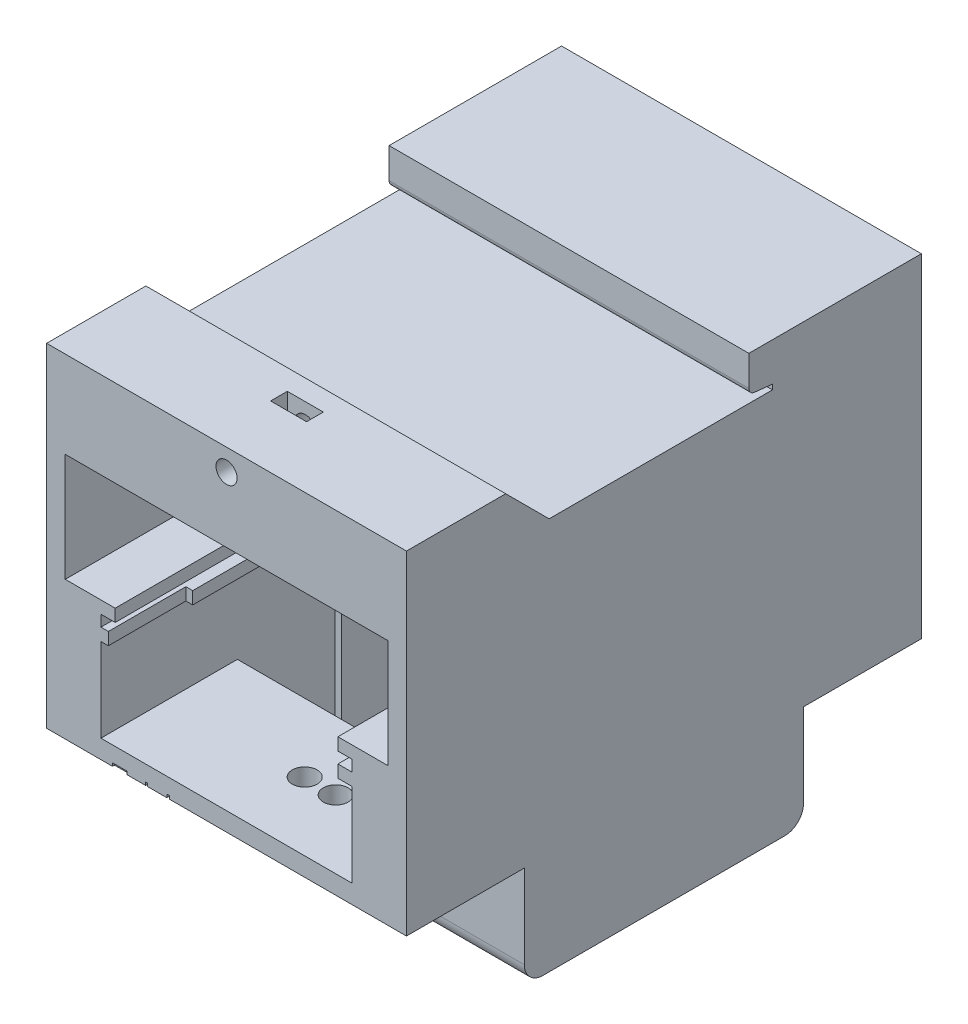
SolidWorks part; units mm, degrees
ref_plane "Plan de face" through (0, 0, 0) normal (0, 0, 1) x (1, 0, 0)
ref_plane "Plan de dessus" through (0, 0, 0) normal (0, 1, 0) x (1, 0, 0)
ref_plane "Plan de droite" through (0, 0, 0) normal (1, 0, 0) x (0, 0, -1)
sketch "Esquisse1" plane through (0, 0, 0) normal (0, 0, 1) x (1, 0, 0)
  line L0 (-20.25, 0) -> (-17.95, 0)
  line L1 (-17.95, 0) -> (-17.95, -2)
  line L2 (-17.95, -2) -> (-20.25, -2)
  line L3 (-20.25, -2) -> (-20.25, -15.5)
  line L14 (0, 21.25) -> (-26, 21.25)
  line L15 (-26, 21.25) -> (-26, 3.8)
  line L16 (-26, 3.8) -> (-17.95, 3.8)
  line L17 (-17.95, 3.8) -> (-17.95, 1.8)
  line L18 (-17.95, 1.8) -> (-20.25, 1.8)
  line L19 (-20.25, 1.8) -> (-20.25, 0)
  line L20 (0, 0) -> (0, 31.1961) construction
  line L21 (0, 0) -> (0, -22.5264) construction
  line L22 (-20.25, -15.5) -> (20.25, -15.5)
  line L23 (29, 28.25) -> (-29, 28.25)
  line L24 (-29, 28.25) -> (-29, -18.5)
  line L25 (-29, -18.5) -> (29, -18.5)
  line L26 (29, 28.25) -> (29, -18.5)
  line L27 (20.25, 1.8) -> (20.25, 0)
  line L28 (17.95, 1.8) -> (20.25, 1.8)
  line L29 (17.95, 3.8) -> (17.95, 1.8)
  line L30 (26, 3.8) -> (17.95, 3.8)
  line L31 (26, 21.25) -> (26, 3.8)
  line L32 (0, 21.25) -> (26, 21.25)
  line L33 (20.25, -2) -> (20.25, -15.5)
  line L34 (17.95, -2) -> (20.25, -2)
  line L35 (17.95, 0) -> (17.95, -2)
  line L36 (20.25, 0) -> (17.95, 0)
  point P15 (0, -18.5)
  point P16 (0, 28.25)
  point P22 (0, -15.5)
  dimension "D1" = 40.5
  dimension "D2" = 15.5
  dimension "D3" = 2.3
  dimension "D5" = 3
  dimension "D6" = 7
  dimension "D7" = 3
  dimension "D8" = 2
  dimension "D9" = 1.8
  dimension "D10" = 2
  dimension "D11" = 21.25
  dimension "D12" = 52
extrude "Boss.-Extru.1" add sketch "Esquisse1" along normal blind 65
sketch "Esquisse2" plane through (0, 0, 0) normal (0, 0, 1) x (1, 0, 0)
  line L6 (26, 3.8) -> (-26, 3.8)
  line L7 (-20.25, -2) -> (20.25, -2) construction
  line L14 (-29, 28.25) -> (-29, -18.5)
  line L15 (29, 28.25) -> (-29, 28.25)
  line L16 (29, -18.5) -> (29, 28.25)
  line L17 (-29, -18.5) -> (29, -18.5)
  line L18 (-29, 28.25) -> (-29, -18.5)
  line L19 (29, 28.25) -> (-29, 28.25)
  line L20 (29, -18.5) -> (29, 28.25)
  line L21 (-29, -18.5) -> (29, -18.5)
  line L38 (-17.95, 0) -> (-17.95, -2)
  line L39 (-17.95, -2) -> (-20.25, -2)
  line L40 (-20.25, -2) -> (-20.25, -15.5)
  line L41 (-20.25, -15.5) -> (20.25, -15.5)
  line L42 (20.25, -15.5) -> (20.25, -2)
  line L43 (20.25, -2) -> (17.95, -2)
  line L44 (17.95, -2) -> (17.95, 0)
  line L45 (17.95, 0) -> (20.25, 0)
  line L46 (20.25, 0) -> (20.25, 1.8)
  line L47 (20.25, 1.8) -> (17.95, 1.8)
  line L63 (17.95, 1.8) -> (17.95, 3.8)
  line L64 (17.95, 3.8) -> (26, 3.8)
  line L65 (26, 3.8) -> (26, 21.25)
  line L66 (26, 21.25) -> (-26, 21.25)
  line L67 (-26, 21.25) -> (-26, 3.8)
  line L68 (-26, 3.8) -> (-17.95, 3.8)
  line L69 (-17.95, 3.8) -> (-17.95, 1.8)
  line L70 (-17.95, 1.8) -> (-20.25, 1.8)
  line L71 (-20.25, 1.8) -> (-20.25, 0)
  line L72 (-20.25, 0) -> (-17.95, 0)
  line L75 (-20.25, -2) -> (-20.25, -15.5) construction
  line L76 (-20.25, -15.5) -> (20.25, -15.5) construction
  line L77 (20.25, -15.5) -> (20.25, -2) construction
  line L85 (26, 3.8) -> (26, 21.25)
  line L86 (26, 21.25) -> (-26, 21.25)
  line L87 (-26, 21.25) -> (-26, 3.8)
  dimension "D1" = 0
  dimension "D2" = 0
extrude "Boss.-Extru.2" add sketch "Esquisse2" against normal blind 15
sketch "Esquisse3" plane through (0, 0, -15) normal (0, 0, -1) x (-1, 0, 0)
  line L4 (-29, -18.5) -> (29, -18.5)
  line L5 (29, -18.5) -> (29, 28.25)
  line L6 (29, 28.25) -> (-29, 28.25)
  line L7 (-29, 28.25) -> (-29, -18.5)
  line L8 (-29, -18.5) -> (29, -18.5)
  line L9 (29, -18.5) -> (29, 28.25)
  line L10 (29, 28.25) -> (-29, 28.25)
  line L11 (-29, 28.25) -> (-29, -18.5)
  dimension "D1" = 0
extrude "Boss.-Extru.3" add sketch "Esquisse3" along normal blind 3
sketch "Esquisse4" plane through (0, 0, 65) normal (0, 0, 1) x (1, 0, 0)
  line L0 (-20.25, 0) -> (-17.95, 0) construction
  line L1 (-8.75, -15.1) -> (-19.05, -15.1)
  line L2 (-8.75, -15.1) -> (-8.75, 0)
  line L3 (-8.75, 0) -> (-19.05, 0)
  line L4 (-19.05, -15.1) -> (-19.05, 0)
  line L5 (-8.75, 0) -> (-8.75, -9.1) construction
  line L6 (-8.75, -15.1) -> (-18.75, -15.1) construction
  line L7 (-18.75, -9.1) -> (-18.75, -13.9) construction
  dimension "D1" = 0.3
extrude "Enlèv. mat.-Extru.1" cut sketch "Esquisse4" against normal up to vertex (12.5 mm away)
sketch "Esquisse5" plane through (0, -18.5, 0) normal (0, -1, 0) x (1, 0, 0)
  circle A0 centre (1.5962, 54) radius 1.5 construction
  circle A1 centre (1.5962, 54) radius 1.5 construction
  circle A2 centre (6.5962, 54) radius 1.5 construction
  circle A3 centre (6.5962, 54) radius 1.5 construction
  circle A4 centre (1.5962, 54) radius 2
  circle A5 centre (6.5962, 54) radius 2
  arc A6 (-11.25, 70.5677) -> (-11.25, 67.0677) centre (-11.25, 68.8177) ccw construction
  arc A7 (-11.25, 70.5677) -> (-11.25, 67.0677) centre (-11.25, 68.8177) ccw construction
  arc A8 (-11.25, 67.0677) -> (-11.25, 70.5677) centre (-11.25, 68.8177) ccw construction
  arc A9 (-11.25, 67.0677) -> (-11.25, 70.5677) centre (-11.25, 68.8177) ccw construction
  arc A10 (-16.25, 70.5677) -> (-16.25, 67.0677) centre (-16.25, 68.8177) ccw construction
  arc A11 (-16.25, 70.5677) -> (-16.25, 67.0677) centre (-16.25, 68.8177) ccw construction
  arc A12 (-16.25, 67.0677) -> (-16.25, 70.5677) centre (-16.25, 68.8177) ccw construction
  arc A13 (-16.25, 67.0677) -> (-16.25, 70.5677) centre (-16.25, 68.8177) ccw construction
  arc A14 (-11.25, 71.0677) -> (-11.25, 66.5677) centre (-11.25, 68.8177) ccw construction
  arc A15 (-11.25, 66.5677) -> (-11.25, 71.0677) centre (-11.25, 68.8177) ccw construction
  arc A16 (-16.25, 71.0677) -> (-16.25, 66.5677) centre (-16.25, 68.8177) ccw construction
  arc A17 (-16.25, 66.5677) -> (-16.25, 71.0677) centre (-16.25, 68.8177) ccw construction
  dimension "D1" = 0.5
  dimension "D2" = 0.5
extrude "Enlèv. mat.-Extru.2" cut sketch "Esquisse5" against normal up to next
sketch "Esquisse6" plane through (0, -18.5, 0) normal (0, -1, 0) x (1, 0, 0)
  line L0 (10.4775, 60.689) -> (-2.1281, 60.689) construction
  line L1 (-7.6073, 65.1874) -> (-19.5069, 65.1874) construction
  text T0 "T1 T2"
  text T1 "NL" font "Century Gothic" height 5
extrude "Enlèv. mat.-Extru.3" cut sketch "Esquisse6" against normal blind 0.5
sketch "Esquisse7" plane through (0, -18.5, 0) normal (0, -1, 0) x (1, 0, 0)
  line L0 (-29, 65) -> (-29, -18) construction
  line L1 (-29, 1) -> (29, 1)
  line L2 (-29, 1) -> (-29, 46)
  line L3 (-29, 46) -> (29, 46)
  line L4 (29, 1) -> (29, 46)
  line L5 (29, 65) -> (29, -18) construction
  line L6 (29, -18) -> (-29, -18) construction
  line L7 (-29, 65) -> (-18.3776, 65) construction
  dimension "D1" = 19
  dimension "D2" = 19
extrude "Boss.-Extru.4" add sketch "Esquisse7" along normal blind 16.5
sketch "Esquisse8" plane through (0, -15.5, 0) normal (0, 1, 0) x (1, 0, 0)
  line L0 (-20.25, -65) -> (-20.25, 0) construction
  line L1 (-20.25, -43) -> (20.25, -43)
  line L2 (-20.25, -43) -> (-20.25, -4)
  line L3 (-20.25, -4) -> (20.25, -4)
  line L4 (20.25, -43) -> (20.25, -4)
  line L5 (20.25, -65) -> (20.25, 0) construction
  line L6 (-29, -1) -> (29, -1) construction
  line L7 (29, -46) -> (-29, -46) construction
  dimension "D1" = 3
  dimension "D2" = 3
extrude "Enlèv. mat.-Extru.4" cut sketch "Esquisse8" against normal offset from surface (16.5 mm away) 3 up to face at (0, -35, 23.5)
fillet "Congé2" radius 3 2 edges at (0, -35, 1) (0, -35, 46)
sketch "Esquisse9" plane through (-29, 0, 0) normal (-1, 0, 0) x (0, 0, 1)
  line L1 (-18, 28.25) -> (6, 28.25)
  line L2 (-18, 28.25) -> (-18, 35.25)
  line L3 (-18, 35.25) -> (9.8, 35.25)
  line L4 (9.8, 29.45) -> (9.8, 35.25)
  line L7 (9.8, 29.45) -> (6, 29.05)
  line L8 (6, 29.05) -> (6, 28.25)
  line L10 (65, 28.25) -> (42, 28.25)
  line L11 (65, 28.25) -> (65, 35.25)
  line L12 (65, 35.25) -> (49, 35.25)
  line L13 (42, 28.25) -> (49, 35.25)
  point P12 (32, 32.25)
  point P13 (33.4653, 32.25)
  dimension "D1" = 0.8
  dimension "D2" = 1.2
  dimension "D3" = 3.8
  dimension "D4" = 24
  dimension "D5" = 7
  dimension "D6" = 36
  dimension "D7" = 45
extrude "Boss.-Extru.5" add sketch "Esquisse9" against normal up to surface (58 mm away) up to face at (29, -15.2743, 23.5)
sketch "Esquisse10" plane through (0, -35, 0) normal (0, -1, 0) x (1, 0, 0)
  line L0 (29, 15) -> (-29, 15) construction
  line L1 (29, 4) -> (29, 43) construction
  line L2 (-29, 43) -> (-29, 4) construction
  line L3 (-29, 4) -> (29, 4) construction
  text T0 "TIC -> MQTT" font "Stencil" height 6.5
  dimension "D1" = 11
extrude "Enlèv. mat.-Extru.5" cut sketch "Esquisse10" against normal blind 0.5
hole_wizard "Dégagement M31" positions "Esquisse11" profile "Esquisse13" hole size "M3" standard "Ansi Metric"
sketch "Esquisse11" plane through (0, 0, 65) normal (0, 0, 1) x (1, 0, 0)
  line L0 (-29, 35.25) -> (29, 28.25) construction
  point P0 (0, 31.75)
  point P9 (0, 31.75)
sketch "Esquisse13" plane through (0, 31.75, 65) normal (1, 0, 0) x (0, -1, 0)
  line L0 (0, 0) -> (0, 19.5)
  line L1 (0, 19.5) -> (1.7, 19.5)
  line L2 (1.7, 19.5) -> (1.7, 0)
  line L5 (1.7, 0) -> (0, 0)
  line L11 (0, -6.35) -> (0, 107.95) construction
  dimension "Diamètre du perçage jusqu'au prochain" = 3.4
  dimension "Profondeur du perçage jusqu'au prochain" = 19.5
sketch "Esquisse14" plane through (0, 0, 65) normal (0, 0, 1) x (1, 0, 0)
  line L0 (-2.9, 33.4243) -> (-2.9, 35.25)
  line L1 (0, 28.4014) -> (2.9, 30.0757)
  line L2 (2.9, 30.0757) -> (2.9, 33.4243)
  line L3 (2.9, 33.4243) -> (0, 35.0986) construction
  line L4 (0, 35.0986) -> (-2.9, 33.4243) construction
  line L5 (-2.9, 33.4243) -> (-2.9, 30.0757)
  line L6 (-2.9, 30.0757) -> (0, 28.4014)
  line L7 (29, 35.25) -> (-29, 35.25) construction
  line L8 (-2.9, 35.25) -> (2.9, 35.25)
  line L9 (2.9, 35.25) -> (2.9, 33.4243)
  circle A0 centre (0, 31.75) radius 2.9 construction
  dimension "D1" = 5.8
extrude "Enlèv. mat.-Extru.6" cut sketch "Esquisse14" against normal blind 2.7 from offset 10 offset against normal yes
hole_wizard "Diamètre du perçage Ø1.5 (1.5)1" positions "Esquisse16" profile "Esquisse17" hole size "Ø1.5" standard "Ansi Metric"
sketch "Esquisse16" plane through (0, -35, 0) normal (0, -1, 0) x (-1, 0, 0)
  line L0 (17.95, -52.5) -> (17.95, 0) construction
  line L1 (-17.95, -65) -> (-17.95, 0) construction
  line L2 (13.95, -19.2295) -> (-13.95, -19.2295) construction
  point P0 (13.95, -19.2295)
  point P2 (-13.95, -19.2295)
  dimension "D1" = 4
  dimension "D2" = 4
sketch "Esquisse17" plane through (-13.95, -35, 19.2295) normal (1, 0, 0) x (0, 0, -1)
  line L0 (0, 0) -> (0, 3)
  line L1 (0, 3) -> (0.75, 3)
  line L2 (0.75, 3) -> (0.75, 0)
  line L5 (0.75, 0) -> (0, 0)
  line L11 (0, -6.35) -> (0, 107.95) construction
  dimension "Diamètre du perçage jusqu'au prochain" = 1.5
  dimension "Profondeur du perçage jusqu'au prochain" = 3
sketch "Esquisse18" plane through (0, -32, 0) normal (0, 1, 0) x (1, 0, 0)
  line L0 (-20.25, -4) -> (20.25, -4) construction
  line L1 (-4.5, -4) -> (-3.5, -4)
  line L2 (-4.5, -4) -> (-4.5, -43)
  line L3 (-4.5, -43) -> (-3.5, -43)
  line L4 (-3.5, -4) -> (-3.5, -43)
  line L5 (-20.25, -43) -> (20.25, -43) construction
  line L6 (-4, -4) -> (-4, -43) construction
  dimension "D1" = 1
  dimension "D2" = 4
extrude "Boss.-Extru.6" add sketch "Esquisse18" along normal up to surface (32 mm away) up to face at (19.1, 0, 32.5)
sketch "Esquisse20" plane through (0, -35, 0) normal (0, -1, 0) x (1, 0, 0)
  line L0 (-13.7598, 34.7762) -> (-11.2979, 32.3143)
  line L1 (-11.2979, 32.3143) -> (-11.8871, 31.7462)
  line L2 (-11.8871, 31.7462) -> (-12.0554, 31.7882)
  line L3 (-12.0554, 31.7882) -> (-12.5262, 31.5857)
  line L4 (-12.5262, 31.5857) -> (-12.7288, 31.1149)
  line L5 (-12.7288, 31.1149) -> (-12.5262, 30.6362)
  line L6 (-12.5262, 30.6362) -> (-12.0554, 30.4416)
  line L7 (-12.0554, 30.4416) -> (-11.5767, 30.6362)
  line L8 (-11.5767, 30.6362) -> (-11.3821, 31.1149)
  line L9 (-11.3821, 31.1149) -> (-11.4031, 31.2622)
  line L10 (-11.4031, 31.2622) -> (-10.835, 31.8514)
  line L11 (-10.835, 31.8514) -> (-8.3731, 29.3895)
  line L12 (-8.3731, 29.3895) -> (-8.0943, 29.2948)
  line L13 (-8.0943, 29.2948) -> (-7.8471, 29.4526)
  line L14 (-7.8471, 29.4526) -> (-7.3973, 30.7483)
  line L15 (-7.3973, 30.7483) -> (-7.3737, 32.1012)
  line L16 (-7.3737, 32.1012) -> (-7.7761, 33.4029)
  line L17 (-7.7761, 33.4029) -> (-8.6046, 34.5447)
  line L18 (-8.6046, 34.5447) -> (-9.7464, 35.3732)
  line L19 (-9.7464, 35.3732) -> (-11.0481, 35.7756)
  line L20 (-11.0481, 35.7756) -> (-12.401, 35.752)
  line L21 (-12.401, 35.752) -> (-13.6967, 35.3022)
  line L22 (-13.6967, 35.3022) -> (-13.8545, 35.055)
  line L23 (-13.8545, 35.055) -> (-13.7598, 34.7762)
  line L24 (-18.0943, 31.4305) -> (-17.9137, 30.1727)
  line L25 (-17.9137, 30.1727) -> (-17.5128, 29.0022)
  line L26 (-17.5128, 29.0022) -> (-16.9141, 27.9411)
  line L27 (-16.9141, 27.9411) -> (-16.1401, 27.0118)
  line L28 (-16.1401, 27.0118) -> (-15.2133, 26.2363)
  line L29 (-15.2133, 26.2363) -> (-14.156, 25.6368)
  line L30 (-14.156, 25.6368) -> (-12.9907, 25.2357)
  line L31 (-12.9907, 25.2357) -> (-11.7398, 25.0549)
  line L32 (-11.7398, 25.0549) -> (-11.7187, 25.0339)
  line L33 (-11.7187, 25.0339) -> (-11.4794, 25.1417)
  line L34 (-11.4794, 25.1417) -> (-11.3821, 25.3916)
  line L35 (-11.3821, 25.3916) -> (-11.3821, 26.0439)
  line L36 (-11.3821, 26.0439) -> (-11.4689, 26.2832)
  line L37 (-11.4689, 26.2832) -> (-11.6977, 26.3805)
  line L38 (-11.6977, 26.3805) -> (-12.688, 26.5294)
  line L39 (-12.688, 26.5294) -> (-13.6112, 26.8536)
  line L40 (-13.6112, 26.8536) -> (-14.4496, 27.3352)
  line L41 (-14.4496, 27.3352) -> (-15.1854, 27.956)
  line L42 (-15.1854, 27.956) -> (-15.8008, 28.6982)
  line L43 (-15.8008, 28.6982) -> (-16.2782, 29.5437)
  line L44 (-16.2782, 29.5437) -> (-16.5998, 30.4745)
  line L45 (-16.5998, 30.4745) -> (-16.7477, 31.4726)
  line L46 (-16.7477, 31.4726) -> (-16.8608, 31.6936)
  line L47 (-16.8608, 31.6936) -> (-17.0844, 31.7882)
  line L48 (-17.0844, 31.7882) -> (-17.7577, 31.7882)
  line L49 (-17.7577, 31.7882) -> (-18.0076, 31.6804)
  line L50 (-18.0076, 31.6804) -> (-18.1154, 31.4305)
  line L51 (-18.1154, 31.4305) -> (-18.0943, 31.4305)
  line L52 (-16.0743, 31.4095) -> (-15.9347, 30.5656)
  line L53 (-15.9347, 30.5656) -> (-15.6516, 29.7794)
  line L54 (-15.6516, 29.7794) -> (-14.7119, 28.4373)
  line L55 (-14.7119, 28.4373) -> (-13.3699, 27.4977)
  line L56 (-13.3699, 27.4977) -> (-12.5837, 27.2145)
  line L57 (-12.5837, 27.2145) -> (-11.7398, 27.0749)
  line L58 (-11.7398, 27.0749) -> (-11.7187, 27.0538)
  line L59 (-11.7187, 27.0538) -> (-11.4794, 27.1617)
  line L60 (-11.4794, 27.1617) -> (-11.3821, 27.4116)
  line L61 (-11.3821, 27.4116) -> (-11.3821, 28.0849)
  line L62 (-11.3821, 28.0849) -> (-11.4663, 28.3085)
  line L63 (-11.4663, 28.3085) -> (-11.6767, 28.4216)
  line L64 (-11.6767, 28.4216) -> (-12.8162, 28.7237)
  line L65 (-12.8162, 28.7237) -> (-13.7545, 29.3868)
  line L66 (-13.7545, 29.3868) -> (-14.4167, 30.3301)
  line L67 (-14.4167, 30.3301) -> (-14.7277, 31.4726)
  line L68 (-14.7277, 31.4726) -> (-14.8408, 31.6935)
  line L69 (-14.8408, 31.6935) -> (-15.0644, 31.7882)
  line L70 (-15.0644, 31.7882) -> (-15.7377, 31.7882)
  line L71 (-15.7377, 31.7882) -> (-15.9876, 31.6804)
  line L72 (-15.9876, 31.6804) -> (-16.0954, 31.4305)
  line L73 (-16.0954, 31.4305) -> (-16.0743, 31.4095)
  line L74 (11.9784, 35.4617) -> (18.7117, 35.4616)
  line L75 (18.7117, 35.4616) -> (18.9511, 35.5669)
  line L76 (18.9511, 35.5669) -> (19.0484, 35.7983)
  line L77 (19.0484, 35.7983) -> (19.0483, 36.4716)
  line L78 (19.0483, 36.4716) -> (18.951, 36.711)
  line L79 (18.951, 36.711) -> (18.7116, 36.8083)
  line L80 (18.7116, 36.8083) -> (11.9783, 36.8083)
  line L81 (11.9783, 36.8083) -> (11.7469, 36.711)
  line L82 (11.7469, 36.711) -> (11.6416, 36.4716)
  line L83 (11.6416, 36.4716) -> (11.6417, 35.7983)
  line L84 (11.6417, 35.7983) -> (11.7469, 35.5669)
  line L85 (11.7469, 35.5669) -> (11.9784, 35.4617)
  line L86 (7.6017, 28.7283) -> (7.6017, 27.7183)
  line L87 (7.6017, 27.7183) -> (7.7069, 27.4869)
  line L88 (7.7069, 27.4869) -> (7.9384, 27.3817)
  line L89 (7.9384, 27.3817) -> (8.1777, 27.4869)
  line L90 (8.1777, 27.4869) -> (8.275, 27.7183)
  line L91 (8.275, 27.7183) -> (8.275, 28.7283)
  line L92 (8.275, 28.7283) -> (8.9483, 28.7283)
  line L93 (8.9483, 28.7283) -> (8.9483, 27.7183)
  line L94 (8.9483, 27.7183) -> (9.0535, 27.4869)
  line L95 (9.0535, 27.4869) -> (9.285, 27.3817)
  line L96 (9.285, 27.3817) -> (9.5243, 27.4869)
  line L97 (9.5243, 27.4869) -> (9.6216, 27.7183)
  line L98 (9.6216, 27.7183) -> (9.6217, 28.7283)
  line L99 (9.6217, 28.7283) -> (9.9583, 28.7283)
  line L100 (9.9583, 28.7283) -> (10.1977, 28.8335)
  line L101 (10.1977, 28.8335) -> (10.295, 29.065)
  line L102 (10.295, 29.065) -> (10.295, 29.7383)
  line L103 (10.295, 29.7383) -> (10.2085, 30.2782)
  line L104 (10.2085, 30.2782) -> (9.9662, 30.7431)
  line L105 (9.9662, 30.7431) -> (9.5937, 31.1054)
  line L106 (9.5937, 31.1054) -> (9.1167, 31.3375)
  line L107 (9.1167, 31.3375) -> (9.1167, 33.8414)
  line L108 (9.1167, 33.8414) -> (9.2587, 34.2412)
  line L109 (9.2587, 34.2412) -> (9.6217, 34.4516)
  line L110 (9.6217, 34.4516) -> (10.0925, 34.3149)
  line L111 (10.0925, 34.3149) -> (10.295, 33.8625)
  line L112 (10.295, 33.8625) -> (10.295, 33.2733)
  line L113 (10.295, 33.2733) -> (10.4423, 32.5579)
  line L114 (10.4423, 32.5579) -> (10.8421, 31.9687)
  line L115 (10.8421, 31.9687) -> (11.4313, 31.5689)
  line L116 (11.4313, 31.5689) -> (12.1467, 31.4217)
  line L117 (12.1467, 31.4217) -> (12.315, 31.4217)
  line L118 (12.315, 31.4217) -> (12.315, 27.3817)
  line L119 (12.315, 27.3817) -> (12.4219, 26.8605)
  line L120 (12.4219, 26.8605) -> (12.7122, 26.4322)
  line L121 (12.7122, 26.4322) -> (13.1406, 26.1418)
  line L122 (13.1406, 26.1418) -> (13.6617, 26.035)
  line L123 (13.6617, 26.035) -> (17.0283, 26.035)
  line L124 (17.0283, 26.035) -> (17.5583, 26.1418)
  line L125 (17.5583, 26.1418) -> (17.9857, 26.4322)
  line L126 (17.9857, 26.4322) -> (18.2711, 26.8606)
  line L127 (18.2711, 26.8606) -> (18.375, 27.3817)
  line L128 (18.375, 27.3817) -> (18.375, 34.7883)
  line L129 (18.375, 34.7883) -> (12.315, 34.7883)
  line L130 (12.315, 34.7883) -> (12.315, 32.4317)
  line L131 (12.315, 32.4317) -> (12.1467, 32.4317)
  line L132 (12.1467, 32.4317) -> (11.5523, 32.6789)
  line L133 (11.5523, 32.6789) -> (11.305, 33.2733)
  line L134 (11.305, 33.2733) -> (11.305, 33.7994)
  line L135 (11.305, 33.7994) -> (11.1998, 34.4023)
  line L136 (11.1998, 34.4023) -> (10.9052, 34.9146)
  line L137 (10.9052, 34.9146) -> (10.4528, 35.2848)
  line L138 (10.4528, 35.2848) -> (9.8742, 35.4616)
  line L139 (9.8742, 35.4616) -> (9.1985, 35.3893)
  line L140 (9.1985, 35.3893) -> (8.6354, 35.0566)
  line L141 (8.6354, 35.0566) -> (8.2497, 34.5266)
  line L142 (8.2497, 34.5266) -> (8.1067, 33.8625)
  line L143 (8.1067, 33.8625) -> (8.1067, 31.3375)
  line L144 (8.1067, 31.3375) -> (7.6385, 31.1054)
  line L145 (7.6385, 31.1054) -> (7.265, 30.7431)
  line L146 (7.265, 30.7431) -> (7.0178, 30.2782)
  line L147 (7.0178, 30.2782) -> (6.9284, 29.7383)
  line L148 (6.9284, 29.7383) -> (6.9284, 29.065)
  line L149 (6.9284, 29.065) -> (7.0336, 28.8335)
  line L150 (7.0336, 28.8335) -> (7.2651, 28.7283)
  line L151 (7.2651, 28.7283) -> (7.6017, 28.7283)
  line L152 (13.5776, 29.7383) -> (15.5554, 32.6631)
  line L153 (15.5554, 32.6631) -> (15.7658, 32.7683)
  line L154 (15.7658, 32.7683) -> (15.971, 32.6894)
  line L155 (15.971, 32.6894) -> (16.0183, 32.5158)
  line L156 (16.0183, 32.5158) -> (15.5343, 30.7483)
  line L157 (15.5343, 30.7483) -> (16.7758, 30.7483)
  line L158 (16.7758, 30.7483) -> (16.9731, 30.6799)
  line L159 (16.9731, 30.6799) -> (17.0283, 30.5169)
  line L160 (17.0283, 30.5169) -> (16.6916, 28.2654)
  line L161 (16.6916, 28.2654) -> (16.4391, 28.055)
  line L162 (16.4391, 28.055) -> (15.0083, 28.055)
  line L163 (15.0083, 28.055) -> (14.8216, 28.147)
  line L164 (14.8216, 28.147) -> (14.7769, 28.3496)
  line L165 (14.7769, 28.3496) -> (15.0083, 29.4017)
  line L166 (15.0083, 29.4017) -> (13.809, 29.4017)
  line L167 (13.809, 29.4017) -> (13.5907, 29.5148)
  line L168 (13.5907, 29.5148) -> (13.5776, 29.7383)
  line L169 (40.8425, 17.0939) -> (39.2012, 15.4527) construction
  line L170 (39.2012, 15.4527) -> (39.1065, 15.2212) construction
  line L171 (39.1065, 15.2212) -> (39.2012, 14.9897) construction
  line L172 (39.2012, 14.9897) -> (39.6852, 14.5058) construction
  line L173 (39.6852, 14.5058) -> (39.9166, 14.4111) construction
  line L174 (39.9166, 14.4111) -> (40.1481, 14.5058) construction
  line L175 (40.1481, 14.5058) -> (41.7893, 16.147) construction
  line L176 (41.7893, 16.147) -> (43.5568, 14.3795) construction
  line L177 (43.5568, 14.3795) -> (42.8634, 14.1589) construction
  line L178 (42.8634, 14.1589) -> (42.3022, 13.7194) construction
  line L179 (42.3022, 13.7194) -> (41.9264, 13.1101) construction
  line L180 (41.9264, 13.1101) -> (41.7893, 12.3806) construction
  line L181 (41.7893, 12.3806) -> (41.9481, 11.5945) construction
  line L182 (41.9481, 11.5945) -> (42.3811, 10.9524) construction
  line L183 (42.3811, 10.9524) -> (43.0232, 10.5194) construction
  line L184 (43.0232, 10.5194) -> (43.8093, 10.3606) construction
  line L185 (43.8093, 10.3606) -> (46.8394, 10.3606) construction
  line L186 (46.8394, 10.3606) -> (47.0787, 10.4658) construction
  line L187 (47.0787, 10.4658) -> (47.176, 10.6973) construction
  line L188 (47.176, 10.6973) -> (47.176, 16.0839) construction
  line L189 (47.176, 16.0839) -> (47.0786, 16.3233) construction
  line L190 (47.0786, 16.3233) -> (46.8393, 16.4206) construction
  line L191 (46.8393, 16.4206) -> (46.166, 16.4206) construction
  line L192 (46.166, 16.4206) -> (45.9345, 16.3233) construction
  line L193 (45.9345, 16.3233) -> (45.8293, 16.0839) construction
  line L194 (45.8293, 16.0839) -> (45.8294, 14.4006) construction
  line L195 (45.8294, 14.4006) -> (45.4506, 14.4006) construction
  line L196 (45.4506, 14.4006) -> (42.7572, 17.0939) construction
  line L197 (42.7572, 17.0939) -> (44.3985, 18.7562) construction
  line L198 (44.3985, 18.7562) -> (44.4932, 18.9877) construction
  line L199 (44.4932, 18.9877) -> (44.3985, 19.2191) construction
  line L200 (44.3985, 19.2191) -> (43.9145, 19.7031) construction
  line L201 (43.9145, 19.7031) -> (43.6831, 19.7978) construction
  line L202 (43.6831, 19.7978) -> (43.4516, 19.7031) construction
  line L203 (43.4516, 19.7031) -> (41.7893, 18.0618) construction
  line L204 (41.7893, 18.0618) -> (40.1481, 19.7031) construction
  line L205 (40.1481, 19.7031) -> (39.9166, 19.7978) construction
  line L206 (39.9166, 19.7978) -> (39.6851, 19.7031) construction
  line L207 (39.6851, 19.7031) -> (39.2012, 19.2191) construction
  line L208 (39.2012, 19.2191) -> (39.1065, 18.9877) construction
  line L209 (39.1065, 18.9877) -> (39.2012, 18.7562) construction
  line L210 (39.2012, 18.7562) -> (40.8425, 17.0939) construction
  line L211 (45.8293, 11.7072) -> (43.8094, 11.7072) construction
  line L212 (43.8094, 11.7072) -> (43.3385, 11.9098) construction
  line L213 (43.3385, 11.9098) -> (43.136, 12.3806) construction
  line L214 (43.136, 12.3806) -> (43.3385, 12.8593) construction
  line L215 (43.3385, 12.8593) -> (43.8094, 13.0539) construction
  line L216 (43.8094, 13.0539) -> (45.8294, 13.0539) construction
  line L217 (45.8294, 13.0539) -> (45.8293, 11.7072) construction
extrude "Enlèv. mat.-Extru.7" cut sketch "Esquisse20" against normal blind 1 and the other way through all
sketch "Esquisse21" plane through (0, 0, 0) normal (0, 0, 1) x (1, 0, 0)
  line L4 (-4.5, -15.5) -> (-3.5, -15.5)
  line L5 (-3.5, -15.5) -> (-3.5, 0)
  line L6 (-3.5, 0) -> (-4.5, 0)
  line L7 (-4.5, 0) -> (-4.5, -15.5)
  line L8 (-4.5, -15.5) -> (-3.5, -15.5)
  line L9 (-3.5, -15.5) -> (-3.5, 0)
  line L10 (-3.5, 0) -> (-4.5, 0)
  line L11 (-4.5, 0) -> (-4.5, -15.5)
  dimension "D1" = 0
extrude "Boss.-Extru.7" add sketch "Esquisse21" along normal up to next
fillet "Congé3" radius 1 1 edges at (0, 29.45, 9.8)
